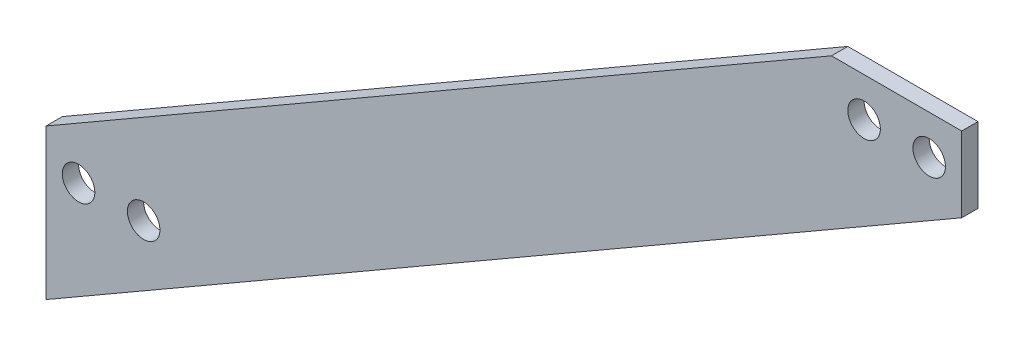
SolidWorks part; units mm, degrees
ref_plane "Front Plane" through (0, 0, 0) normal (0, 0, 1) x (1, 0, 0)
ref_plane "Top Plane" through (0, 0, 0) normal (0, 1, 0) x (1, 0, 0)
ref_plane "Right Plane" through (0, 0, 0) normal (1, 0, 0) x (0, 0, -1)
sketch "Sketch1" plane through (0, 0, 0) normal (0, 0, 1) x (1, 0, 0)
  line L0 (0, 0) -> (0, -43.9941)
  line L1 (0, -43.9941) -> (267.97, 110.7185)
  line L2 (267.97, 110.7185) -> (267.97, 132.7155)
  line L3 (267.97, 132.7155) -> (229.87, 132.7155)
  line L4 (229.87, 132.7155) -> (0, 0)
  line L5 (248.92, 129.8539) -> (267.97, 129.8539) construction
  circle A0 centre (9.525, -9.7041) radius 4.7625
  circle A1 centre (28.575, -9.7041) radius 4.7625
  circle A2 centre (239.395, 121.2855) radius 4.7625
  circle A3 centre (258.445, 121.2855) radius 4.7625
  point P16 (258.445, 129.8539)
  point P17 (248.92, 132.7155)
  dimension "D5" = 9.525
  dimension "D9" = 9.525
  dimension "D1" = 38.1
  dimension "D2" = 60
  dimension "D3" = 267.97
  dimension "D4" = 38.1
  dimension "D6" = 19.05
  dimension "D7" = 9.525
  dimension "D8" = 34.29
  dimension "D10" = 19.05
  dimension "D12" = 11.43
extrude "Boss-Extrude1" add sketch "Sketch1" along normal blind 4.7625
